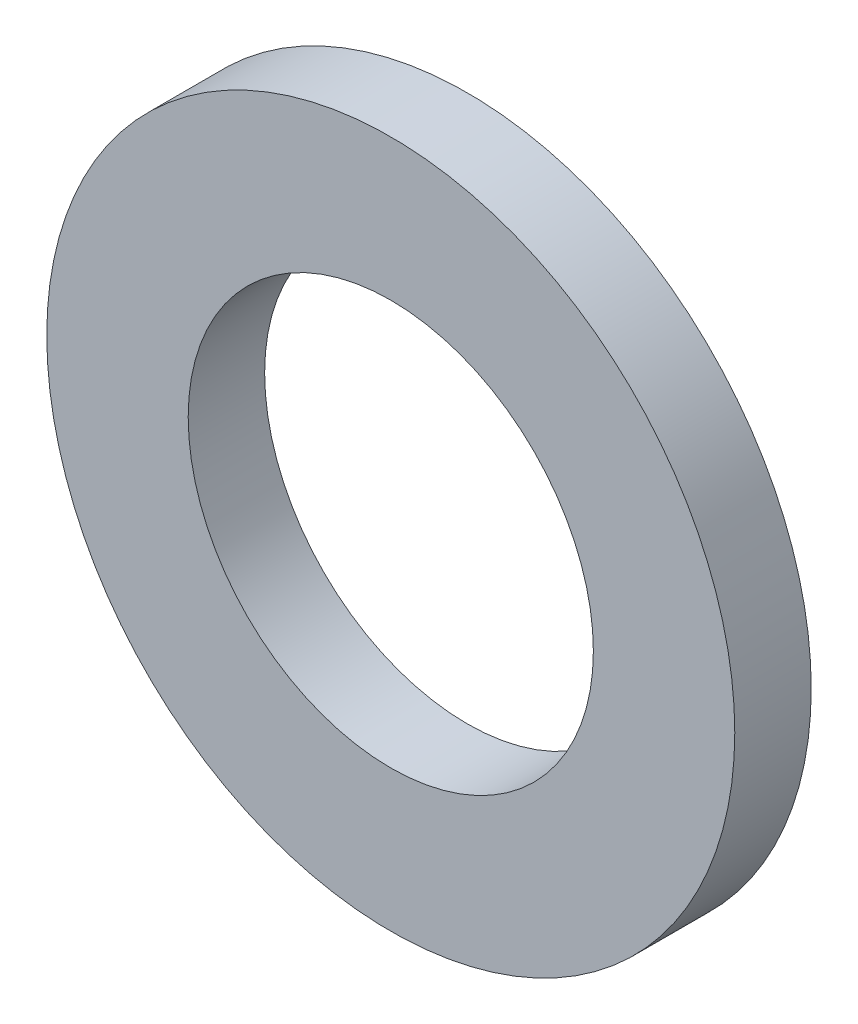
SolidWorks part; units mm, degrees
material "Cast Stainless Steel"
ref_plane "Front Plane" through (0, 0, 0) normal (0, 0, 1) x (1, 0, 0)
ref_plane "Top Plane" through (0, 0, 0) normal (0, 1, 0) x (1, 0, 0)
ref_plane "Right Plane" through (0, 0, 0) normal (1, 0, 0) x (0, 0, -1)
sketch "Sketch1" plane through (0, 0, 0) normal (0, 0, 1) x (1, 0, 0)
  circle A0 centre (0, 0) radius 4.5
  circle A1 centre (0, 0) radius 2.65
  dimension "OD" = 9
  dimension "ID1" = 5.3
extrude "Boss-Extrude1" add sketch "Sketch1" along normal blind 1
ref_axis "Center Axis 1" through (0, 0, 1) along (0, 0, -1)
ref_plane "Contact Plane 1" through (0, 0, 1) normal (0, 0, 1) x (1, 0, 0)
ref_plane "Contact Plane 2" through (0, 0, 0) normal (0, 0, -1) x (-1, 0, 0)
move or copy body "Body-Move/Copy1" [suppressed] bodies to move or copy 101
